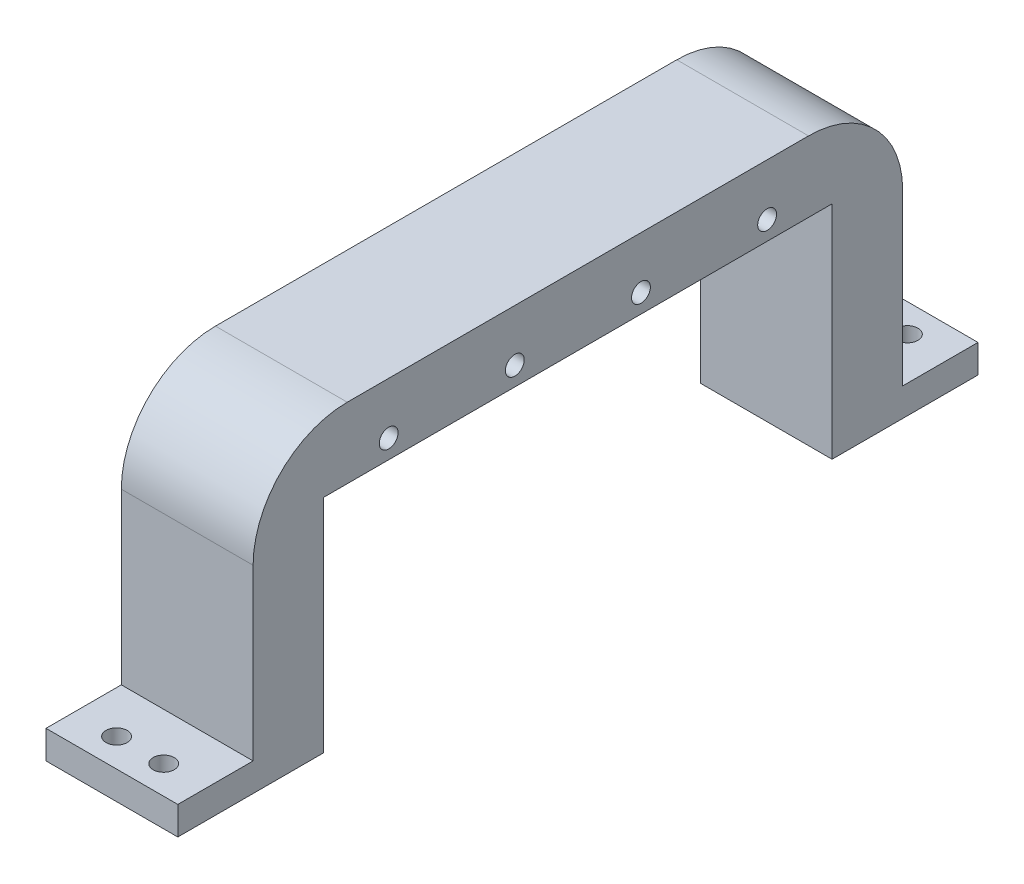
SolidWorks part; units mm, degrees
ref_plane "Front Plane" through (0, 0, 0) normal (0, 0, 1) x (1, 0, 0)
ref_plane "Top Plane" through (0, 0, 0) normal (0, 1, 0) x (1, 0, 0)
ref_plane "Right Plane" through (0, 0, 0) normal (1, 0, 0) x (0, 0, -1)
sketch "Sketch1" plane through (0, 0, 0) normal (1, 0, 0) x (0, 0, -1)
  line L0 (0, 0) -> (0, 9.568) construction
  line L1 (-27, 0) -> (27, 0)
  line L2 (27, 0) -> (27, -23.5)
  line L3 (27, -23.5) -> (34.5, -23.5)
  line L4 (34.5, -23.5) -> (34.5, 7.5)
  line L5 (34.5, 7.5) -> (-34.5, 7.5)
  line L6 (-34.5, -23.5) -> (-34.5, 7.5)
  line L7 (-27, -23.5) -> (-34.5, -23.5)
  line L8 (-27, 0) -> (-27, -23.5)
  point P9 (0, 7.5)
  dimension "D1" = 54
  dimension "D2" = 7.5
  dimension "D3" = 7.5
  dimension "D4" = 23.5
extrude "Boss-Extrude1" add sketch "Sketch1" along normal blind 7 and the other way blind 7
fillet "Fillet1" radius 10 2 edges at (0, 7.5, 34.5) (0, 7.5, -34.5)
sketch "Sketch2" plane through (7, 0, 0) normal (1, 0, 0) x (0, 0, -1)
  line L0 (0, 0) -> (0, 7.5) construction
  line L1 (24.5, 7.5) -> (-24.5, 7.5) construction
  line L2 (-27, 0) -> (27, 0) construction
  circle A0 centre (-6.7, 2) radius 1
  circle A1 centre (-20.1, 2) radius 1
  circle A2 centre (20.1, 2) radius 1
  circle A3 centre (6.7, 2) radius 1
  point P11 (0, 0)
  dimension "D4" = 2
  dimension "D5" = 2
  dimension "D1" = 2
  dimension "D2" = 6.7
  dimension "D3" = 13.4
extrude "Cut-Extrude1" cut sketch "Sketch2" against normal through all
sketch "Sketch3" plane through (0, -23.5, 0) normal (0, -1, 0) x (1, 0, 0)
  line L0 (0, -27) -> (0, -34.5) construction
  line L1 (-7, -27) -> (7, -27) construction
  line L2 (-7, -34.5) -> (7, -34.5) construction
  line L3 (-7, -30.75) -> (7, -30.75) construction
  line L4 (-7, -27) -> (-7, -34.5) construction
  line L5 (7, -27) -> (7, -34.5) construction
  line L6 (0, 0) -> (7, 0) construction
  line L7 (7, 27) -> (7, -27) construction
  circle A0 centre (-2.5, -30.75) radius 1
  circle A1 centre (2.5, -30.75) radius 1
  circle A2 centre (-2.5, 30.75) radius 1
  circle A3 centre (2.5, 30.75) radius 1
  dimension "D1" = 2
  dimension "D2" = 2.5
extrude "Cut-Extrude2" cut sketch "Sketch3" against normal blind 5
sketch "Sketch4" plane through (0, -23.5, 0) normal (0, -1, 0) x (1, 0, 0)
  line L0 (0, 0) -> (7, 0) construction
  line L1 (-7, 34.5) -> (7, 34.5)
  line L2 (-7, 34.5) -> (-7, 42.5)
  line L3 (-7, 42.5) -> (7, 42.5)
  line L4 (7, 34.5) -> (7, 42.5)
  line L5 (7, 27) -> (7, -27) construction
  line L6 (7, 34.5) -> (7, 27) construction
  line L7 (0, 39.5) -> (0, 42.5) construction
  line L8 (0, -39.5) -> (0, -42.5) construction
  line L9 (-7, -39.5) -> (7, -39.5) construction
  line L10 (7, -34.5) -> (7, -42.5)
  line L11 (-7, -42.5) -> (7, -42.5)
  line L12 (-7, -34.5) -> (-7, -42.5)
  line L13 (-7, -34.5) -> (7, -34.5)
  circle A0 centre (-2.5, 39.5) radius 1.1229
  circle A1 centre (2.5, 39.5) radius 1.1229
  circle A2 centre (2.5, -39.5) radius 1.1229
  circle A3 centre (-2.5, -39.5) radius 1.1229
  point P10 (-2.9149, 40.9662)
  dimension "D1" = 8
  dimension "D2" = 2.5
  dimension "D3" = 3
extrude "Boss-Extrude2" add sketch "Sketch4" against normal blind 3
